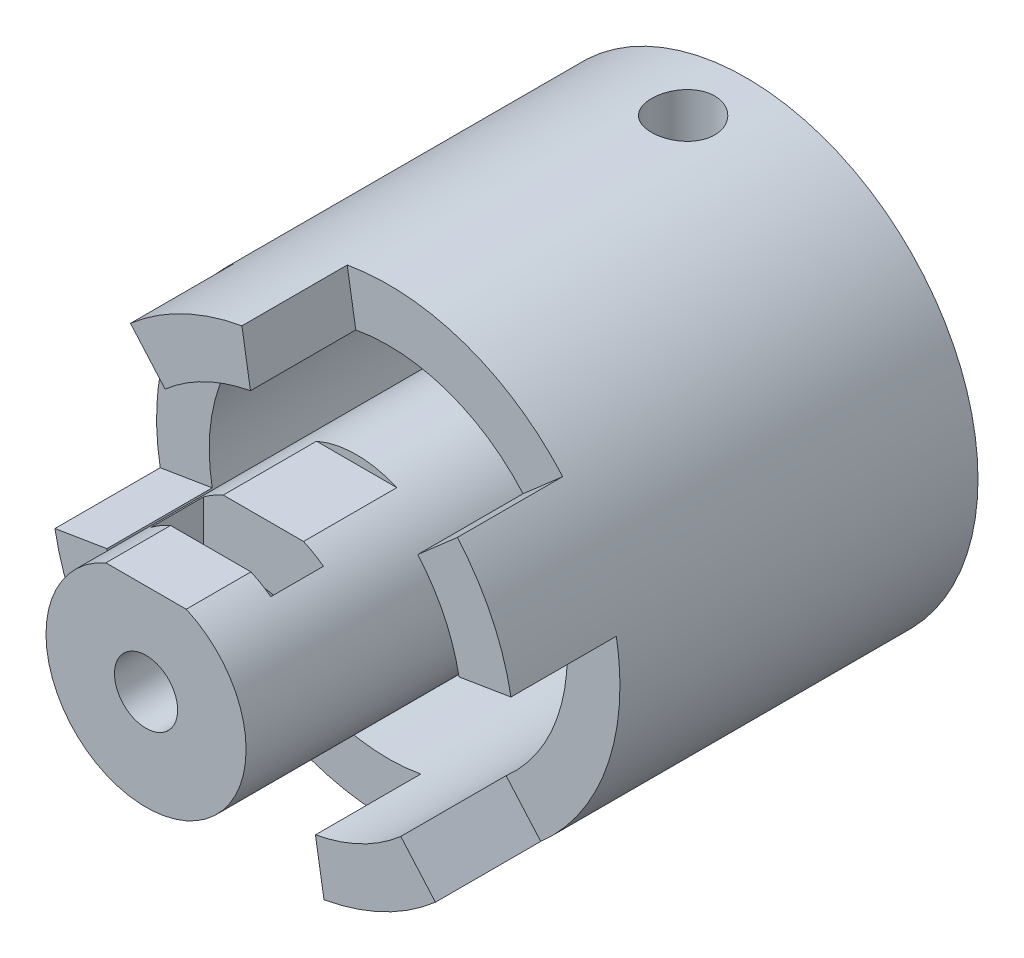
SolidWorks part; units mm, degrees
ref_plane "Front Plane" through (0, 0, 0) normal (0, 0, 1) x (1, 0, 0)
ref_plane "Top Plane" through (0, 0, 0) normal (0, 1, 0) x (1, 0, 0)
ref_plane "Right Plane" through (0, 0, 0) normal (1, 0, 0) x (0, 0, -1)
sketch "Sketch3" plane through (0, 0, 0) normal (1, 0, 0) x (0, 0, -1)
  line L0 (-7.3374, 0) -> (14.1626, 0)
  line L1 (14.1626, 0) -> (14.1626, -3.75)
  line L4 (19.1626, 4.75) -> (-7.3374, 4.75)
  line L5 (-7.3374, 4.75) -> (-7.3374, 0)
  line L6 (-26.8946, 4.75) -> (41.8764, 4.75) construction
  line L7 (14.1626, -3.75) -> (4.1626, -3.75)
  line L8 (4.1626, -3.75) -> (4.1626, -6.25)
  line L9 (4.1626, -6.25) -> (16.1626, -6.25)
  line L16 (21.1626, -3.0474) -> (21.1626, 4.75)
  line L17 (21.1626, 4.75) -> (19.1626, 4.75)
  line L18 (16.1626, -6.25) -> (21.1626, -6.25)
  line L19 (21.1626, -6.25) -> (21.1626, -3.0474)
  dimension "D4" = 3.75
  dimension "D1" = 21.5
  dimension "D2" = 2.5
  dimension "D3" = 4.75
  dimension "D5" = 5
  dimension "D7" = 10
revolve "Revolve1" add sketch "Sketch3" angle 360 about L6
sketch "Sketch4" plane through (0, 0, -4.1626) normal (0, 0, 1) x (1, 0, 0)
  line L0 (0, 4.75) -> (0, 18.75) construction
  line L2 (0, 4.75) -> (-9.8995, 14.6495) construction
  line L6 (-1.9481, 15.5761) -> (-1.543, 13.1088)
  line L7 (-7.2394, 13.0319) -> (-5.5941, 11.1497)
  circle A0 centre (0, 4.75) radius 11 construction
  arc A1 (-1.9481, 15.5761) -> (-7.2394, 13.0319) centre (0, 4.75) ccw
  circle A2 centre (0, 4.75) radius 8.5 construction
  arc A3 (-1.543, 13.1088) -> (-5.5941, 11.1497) centre (0, 4.75) ccw
  dimension "D1" = 4.5
  dimension "D2" = 45
extrude "Boss-Extrude2" add sketch "Sketch4" along normal blind 5
pattern_circular "CirPattern1" count 4 over 360 about axis through (0, 4.75, 7.3374) along (0, 0, 1) of "Boss-Extrude2"
sketch "Sketch5" plane through (0, 0, 7.3374) normal (0, 0, 1) x (1, 0, 0)
  circle A0 centre (0, 4.75) radius 1.5
  circle A1 centre (0, 4.75) radius 4.75
  arc A2 (-2.0215, 9.0484) -> (2.0215, 9.0484) centre (0, 4.75) ccw construction
  dimension "D2" = 3
  dimension "D1" = 0
extrude "Cut-Extrude1" cut sketch "Sketch5" against normal blind 10
sketch "Sketch7" plane through (0, 0, -21.1626) normal (0, 0, -1) x (-1, 0, 0)
  line L0 (-1.445, 6.2738) -> (1.445, 6.2738)
  arc A0 (-1.445, 6.2738) -> (1.445, 6.2738) centre (0, 4.75) ccw
  circle A1 centre (0, 4.75) radius 11
  circle A4 centre (0, 4.75) radius 11 construction
  dimension "D2" = 4.2
  dimension "D3" = 2.89
  dimension "D1" = 0
extrude "Cut-Extrude2" cut sketch "Sketch7" against normal blind 10
sketch "Sketch8" plane through (0, 0, -21.1626) normal (0, 0, -1) x (-1, 0, 0)
  line L0 (0, 4.75) -> (0, 9.3583) construction
  line L1 (-2.825, 7.2738) -> (2.825, 7.2738)
  line L2 (-2.825, 7.2738) -> (-2.825, 9.7738)
  line L3 (-2.825, 9.7738) -> (2.825, 9.7738)
  line L4 (2.825, 7.2738) -> (2.825, 9.7738)
  line L5 (1.445, 6.2738) -> (-1.445, 6.2738) construction
  dimension "D1" = 5.65
  dimension "D2" = 2.5
  dimension "D3" = 2.825
  dimension "D4" = 1
extrude "Cut-Extrude3" cut sketch "Sketch8" against normal blind 6.5
sketch "Sketch10" plane through (0, 6.2738, 0) normal (0, -1, 0) x (1, 0, 0)
  line L0 (-11, -21.1626) -> (11, -21.1626) construction
  circle A0 centre (0, -18.1626) radius 1.5
  dimension "D1" = 3
  dimension "D2" = 3
extrude "Cut-Extrude5" cut sketch "Sketch10" against normal blind 10
sketch "Sketch12" plane through (0, 0, 7.3374) normal (0, 0, 1) x (1, 0, 0)
  line L0 (-1.9075, 9.1002) -> (1.9075, 9.1002)
  circle A0 centre (0, 4.75) radius 4.75 construction
  arc A1 (1.9075, 9.1002) -> (-1.9075, 9.1002) centre (0, 4.75) ccw
extrude "Cut-Extrude6" cut sketch "Sketch12" against normal blind 10
sketch "Sketch13" plane through (0, 9.1002, 0) normal (0, 1, 0) x (1, 0, 0)
  line L0 (0, 0) -> (0, -5.5754) construction
  line L1 (-2.85, -4.2654) -> (2.85, -4.2654)
  line L2 (-2.85, -4.2654) -> (-2.85, -1.7654)
  line L3 (-2.85, -1.7654) -> (2.85, -1.7654)
  line L4 (2.85, -4.2654) -> (2.85, -1.7654)
  dimension "D1" = 5.7
  dimension "D2" = 2.85
  dimension "D3" = 2.5
extrude "Cut-Extrude7" cut sketch "Sketch13" against normal blind 7.5
